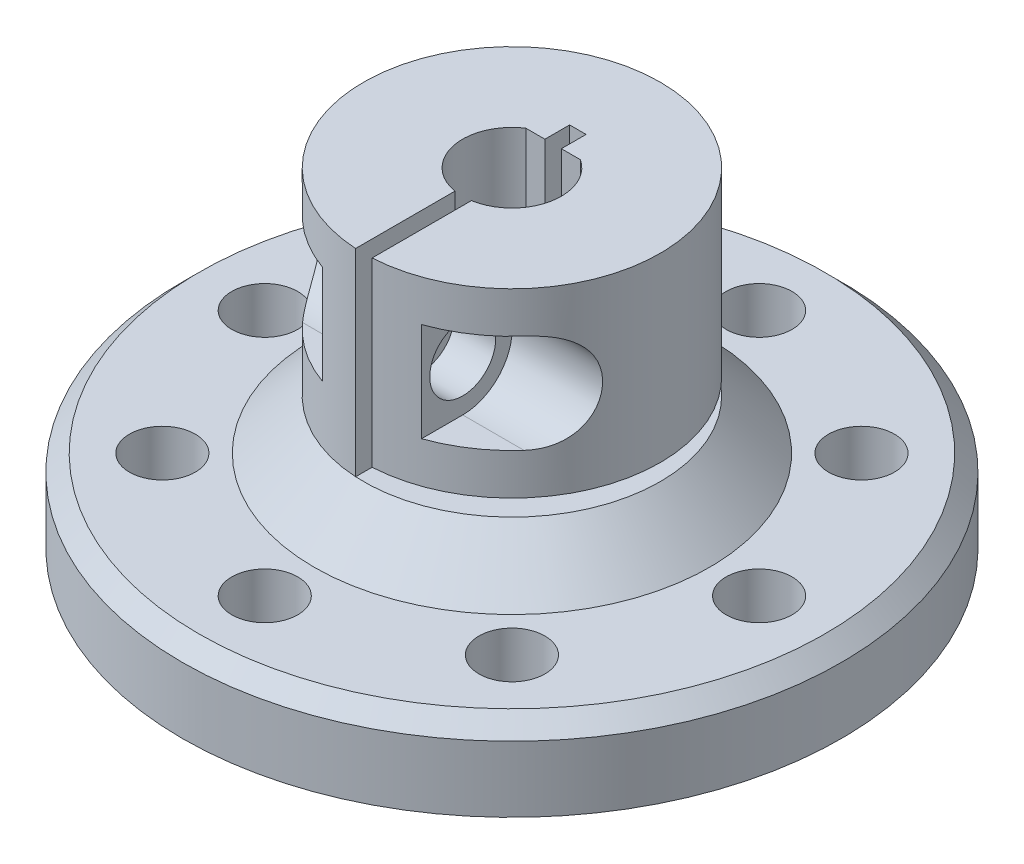
SolidWorks part; units mm, degrees
material "PLA"
ref_plane "Front" through (0, 0, 0) normal (0, 0, 1) x (1, 0, 0)
ref_plane "Top" through (0, 0, 0) normal (0, 1, 0) x (1, 0, 0)
ref_plane "Right" through (0, 0, 0) normal (1, 0, 0) x (0, 0, -1)
sketch "Sketch1" plane through (0, 0, 0) normal (0, 1, 0) x (1, 0, 0)
  circle A0 centre (0, 0) radius 20
  dimension "D1" = 40
extrude "Boss-Extrude1" add sketch "Sketch1" along normal blind 5
sketch "Sketch2" plane through (0, 5, 0) normal (0, 1, 0) x (1, 0, 0)
  circle A0 centre (0, 15) radius 2
  circle A1 centre (10.6066, 10.6066) radius 2
  circle A2 centre (15, 0) radius 2
  circle A3 centre (10.6066, -10.6066) radius 2
  circle A4 centre (0, -15) radius 2
  circle A5 centre (-10.6066, -10.6066) radius 2
  circle A6 centre (-15, 0) radius 2
  circle A7 centre (-10.6066, 10.6066) radius 2
  point P19 (0, 0)
  dimension "D1" = 4
  dimension "D2" = 15
  dimension "D3" = 8
extrude "Cut-Extrude1" cut sketch "Sketch2" against normal through all
sketch "Sketch3" plane through (0, 5, 0) normal (0, 1, 0) x (1, 0, 0)
  circle A0 centre (0, 0) radius 9
  dimension "D1" = 18
extrude "Boss-Extrude2" add sketch "Sketch3" along normal blind 15
sketch "Sketch4" plane through (0, 20, 0) normal (0, 1, 0) x (1, 0, 0)
  line L0 (-1.6583, 2.5) -> (1.6583, 2.5)
  line L1 (0, 0) -> (0, -3) construction
  circle A0 centre (0, 0) radius 3
  dimension "D1" = 6
  dimension "D2" = 5.5
extrude "Cut-Extrude2" cut sketch "Sketch4" against normal through all contours L0 A0 region at (0, 20, 0.112)
sketch "Sketch5" plane through (0, 20, 0) normal (0, 1, 0) x (1, 0, 0)
  line L1 (-0.5, -9) -> (0.5, -9)
  line L2 (-0.5, -9) -> (-0.5, 4)
  line L3 (-0.5, 4) -> (0.5, 4)
  line L4 (0.5, -9) -> (0.5, 4)
  line L5 (-0.5, -9) -> (0.5, 4) construction
  line L6 (-0.5, 4) -> (0.5, -9) construction
  circle A0 centre (0, 0) radius 9 construction
  point P0 (0, -2.5)
  dimension "D1" = 1
  dimension "D2" = 4
extrude "Cut-Extrude3" cut sketch "Sketch5" against normal blind 12
ref_plane "Plane1" through (9, 0, 0) normal (1, 0, 0) x (0, 0, -1)
sketch "Sketch7" plane through (9, 0, 0) normal (1, 0, 0) x (0, 0, -1)
  line L0 (9, 5) -> (9, 20) construction
  line L1 (9, 8) -> (-8.9861, 8)
  line L2 (9, 8) -> (9, 9)
  line L3 (9, 9) -> (-8.9861, 9)
  line L4 (-8.9861, 8) -> (-8.9861, 9)
  line L5 (-8.9861, 20) -> (-8.9861, 8) construction
  line L6 (-8.9861, 8) -> (-9, 8) construction
  dimension "D1" = 1
extrude "Cut-Extrude4" cut sketch "Sketch7" against normal up to surface (9.5 mm away) up to face at (-0.5, 14, 5.9721)
sketch "Sketch8" plane through (9, 0, 0) normal (1, 0, 0) x (0, 0, -1)
  line L0 (-8.9861, 20) -> (-8.9861, 9) construction
  line L1 (-5.9861, 17.5) -> (-8.9861, 17.5)
  line L2 (-8.9861, 17.5) -> (-8.9861, 11.5)
  line L3 (-8.9861, 11.5) -> (-5.9861, 11.5)
  line L4 (9, 9) -> (9, 20) construction
  line L5 (9, 14.5) -> (-17.854, 14.5) construction
  circle A0 centre (-5.9861, 14.5) radius 3
  dimension "D1" = 6
extrude "Cut-Extrude5" cut sketch "Sketch8" against normal blind 6 contours A0 | A0 L1 L2 | A0 L2 L3 region at (9, 16.8299, 8.316) region at (9, 14.5, 5.9861) region at (9, 12.1701, 8.316)
mirror "Mirror1" about plane through (0, 0, 0) normal (1, 0, 0) of "Cut-Extrude5"
sketch "Sketch9" plane through (3, 0, 0) normal (1, 0, 0) x (0, 0, -1)
  circle A0 centre (-5.9861, 14.5) radius 2
  arc A1 (-5.9861, 11.5) -> (-5.9861, 17.5) centre (-5.9861, 14.5) ccw construction
  dimension "D1" = 4
extrude "Cut-Extrude6" cut sketch "Sketch9" against normal through all
chamfer "Chamfer3" distance 3 distance2 3 1 edges at (0, 5, 9)
chamfer "Chamfer4" distance 1 angle 45 1 edges at (0, 5, 20)
